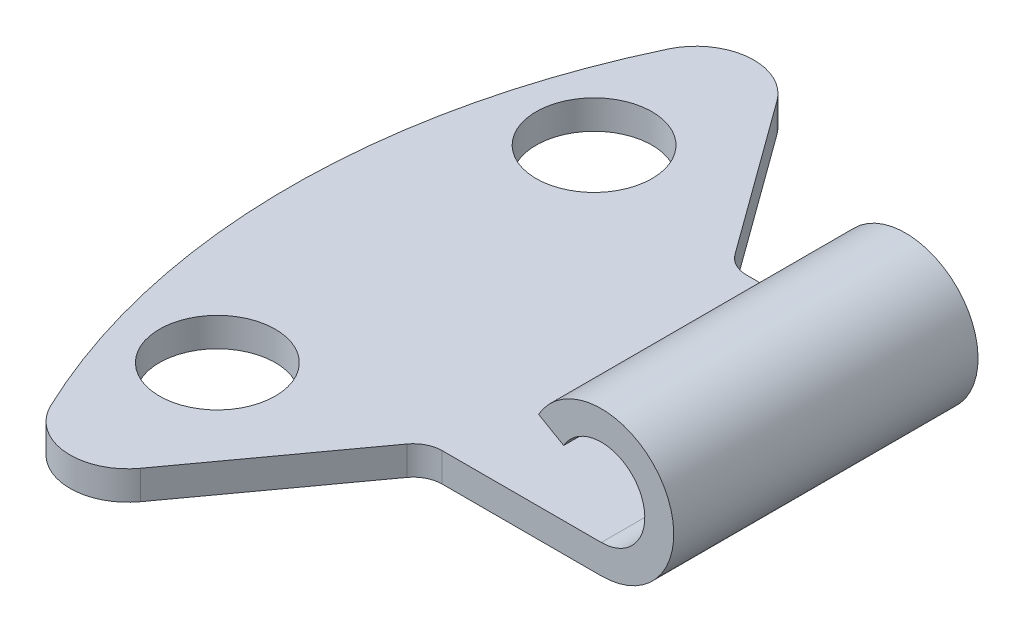
SolidWorks part; units mm, degrees
material "Acciaio inossidabile fuso"
ref_plane "Piano frontale" through (0, 0, 0) normal (0, 0, 1) x (1, 0, 0)
ref_plane "Piano superiore" through (0, 0, 0) normal (0, 1, 0) x (1, 0, 0)
ref_plane "Piano destro" through (0, 0, 0) normal (1, 0, 0) x (0, 0, -1)
sketch "Schizzo1" plane through (0, 0, 0) normal (0, 0, 1) x (1, 0, 0)
  line L0 (8, 1) -> (8, 2.5) construction
  line L1 (-8, 1) -> (8, 1)
  line L2 (-8, 1) -> (-8, 0)
  line L3 (-8, 0) -> (8, 0)
  line L5 (5.8349, 3.75) -> (6.701, 3.25)
  arc A0 (8, 0) -> (5.8349, 3.75) centre (8, 2.5) ccw
  arc A1 (8, 1) -> (6.701, 3.25) centre (8, 2.5) ccw
  point P4 (4.3364, 7.1131)
  point P6 (0, 0)
  dimension "D3" = 3
  dimension "D4" = 1
  dimension "D1" = 16
  dimension "D2" = 1
  dimension "D5" = 120
extrude "Estrusione-Estrusione1" add sketch "Schizzo1" along normal blind 27
sketch "Schizzo2" plane through (0, 1, 0) normal (0, 1, 0) x (1, 0, 0)
  line L0 (-4, -20) -> (-4, -7) construction
  line L1 (-8, -27) -> (-8, 0) construction
  line L2 (-4, -13.5) -> (-8, -13.5) construction
  line L3 (12, -8.25) -> (2.5092, -8.25)
  line L5 (12, -18.75) -> (2.5092, -18.75)
  line L6 (2, -8.25) -> (2, -18.75) construction
  line L7 (2, -13.5) -> (-4, -13.5) construction
  line L8 (1.7005, -19.1618) -> (-2.166, -24.4783)
  line L9 (8, -27) -> (-8, -27) construction
  line L10 (1.7005, -7.8382) -> (-2.166, -2.5217)
  line L11 (8, 0) -> (-8, 0) construction
  line L12 (12, -18.75) -> (12, -27)
  line L13 (12, -27) -> (-8, -27)
  line L14 (-8, -27) -> (-8, -13.5)
  line L15 (12, 0) -> (12, -8.25)
  line L16 (12, 0) -> (-8, 0)
  line L17 (-8, 0) -> (-8, -13.5)
  circle A0 centre (-4, -7) radius 2
  circle A1 centre (-4, -20) radius 2
  arc A2 (-5.5889, -24.1624) -> (-5.5889, -2.8376) centre (16.7813, -13.5) cw
  arc A3 (-2.166, -2.5217) -> (-5.5889, -2.8376) centre (-3.7835, -3.6981) ccw
  arc A4 (-2.166, -24.4783) -> (-5.5889, -24.1624) centre (-3.7835, -23.3019) cw
  arc A5 (2.5092, -18.75) -> (1.7005, -19.1618) centre (2.5092, -19.75) ccw
  arc A6 (2.5092, -8.25) -> (1.7005, -7.8382) centre (2.5092, -7.25) cw
  point P26 (-4, 0)
  point P29 (-4, -27)
  line M9 (8, 0) -> (-8, 0)
  line M10 (-8, 0) -> (-8, -27)
  line M11 (-8, -27) -> (8, -27)
  line M12 (8, -27) -> (8, 0)
  dimension "D2" = 4
  dimension "D8" = 24.7813
  dimension "D9" = 2
  dimension "D10" = 1
  dimension "D1" = 13
  dimension "D3" = 4
  dimension "D4" = 10.5
  dimension "D5" = 6
  dimension "D6" = 4
  dimension "D7" = 4
  dimension "D11" = 20
extrude "Taglio-Estrusione1" cut sketch "Schizzo2" against normal blind 27 and the other way blind 27 contours L5 A5 L8 A4 A2 M10 M11 M12 | A6 L3 A2 A3 L10 M12 M9 M10 | L13 L12 L5 M12 | L15 L16 L3 M12 | A1 | A0 region at (10, 1, 4.125) region at (1.2738, 1, 3.5405) region at (1.2738, 1, 23.4595) region at (10, 1, 22.875)
